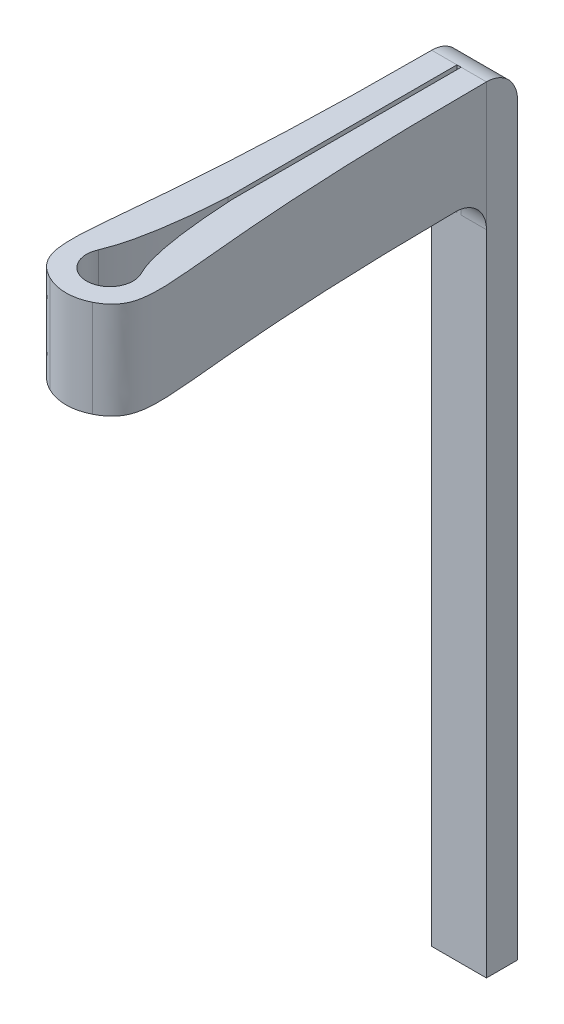
SolidWorks part; units mm, degrees
ref_plane "Front Plane" through (0, 0, 0) normal (0, 0, 1) x (1, 0, 0)
ref_plane "Top Plane" through (0, 0, 0) normal (0, 1, 0) x (1, 0, 0)
ref_plane "Right Plane" through (0, 0, 0) normal (1, 0, 0) x (0, 0, -1)
sketch "Sketch1" plane through (0, 0, 0) normal (0, 1, 0) x (1, 0, 0)
  line L0 (0, 0) -> (0, 6.2146) construction
  line L1 (-0.6908, 2.6065) -> (-0.2172, 3.7387) construction
  line L2 (-0.0683, 13.7149) -> (0.0683, 13.7149)
  line L3 (-0.0683, 13.7149) -> (-0.0683, 6.2146)
  line L5 (0.0683, 13.7149) -> (0.0683, 6.2146)
  line L6 (-0.2172, 3.7387) -> (-0.0683, 6.2146) construction
  line L9 (0.6908, 2.6065) -> (0.2181, 3.4821) construction
  line L10 (0.2181, 3.4821) -> (0.0683, 6.2146) construction
  line L11 (-0.8958, 13.7149) -> (-0.8958, 4.5422) construction
  line L12 (-0.8958, 4.5422) -> (-1.5887, 2.2193) construction
  line L20 (-1.5887, 2.2193) -> (-2.0882, 1.3377) construction
  line L21 (-2.0882, 1.3377) -> (0, 0.7662) construction
  line L22 (0.8958, 13.7149) -> (0.8958, 4.5422) construction
  line L23 (0.8958, 4.5422) -> (1.5887, 2.2193) construction
  line L25 (1.5887, 2.2193) -> (2.0882, 1.3377) construction
  line L26 (2.0882, 1.3377) -> (0, 0.7662) construction
  line L27 (-0.8958, 13.7149) -> (0, 13.7149)
  line L28 (0.8958, 13.7149) -> (0, 13.7149)
  arc A0 (-0.6908, 2.6065) -> (0.6908, 2.6065) centre (0, 2.2849) ccw
  spline S3 degree 2 poles (0.6908, 2.6065) (0.2181, 3.4821) (0.0683, 6.2146) knots 0 0 0 1 1 1
  spline S4 degree 2 poles (-0.6908, 2.6065) (-0.2172, 3.7387) (-0.0683, 6.2146) knots 0 0 0 1 1 1
  spline S5 degree 4 poles (-0.8958, 13.7149) (-0.8958, 4.5422) (-1.5887, 2.2193) (-2.0882, 1.3377) (0, 0.7662) knots 0 0 0 0 0 1 1 1 1 1
  spline S6 degree 4 poles (0.8958, 13.7149) (0.8958, 4.5422) (1.5887, 2.2193) (2.0882, 1.3377) (0, 0.7662) knots 0 0 0 0 0 1 1 1 1 1
  point P8 (-0.508, -2.5134)
  point P18 (0.508, -2.5134)
  point P21 (0, -2.54)
  dimension "D1" = 1.524
  dimension "D2" = 11.43
extrude "Boss-Extrude1" add sketch "Sketch1" along normal blind 1.5875 and the other way blind 1.5875 contours S6 L28 L5 S3 A0 S4 L3 L27 S5 region at (-0.2009, 0, -9.9647)
ref_axis "Axis1" through (0, 0, -2.032) along (0, 0, 1)
ref_plane "Plane1" through (0, 0, 2.54) normal (0, 0, 1) x (1, 0, 0)
ref_axis "Axis2" through (0, 1.7463, 2.54) along (0, -1, 0)
fillet "Fillet1" radius 1.524 1 edges at (0, 0, -0.7662)
ref_plane "Plane2" through (0, 0, -2.6065) normal (0, 0, -1) x (-1, 0, 0)
ref_plane "Plane3" through (0, 0, -3.1145) normal (0, 0, -1) x (-1, 0, 0)
sketch "Sketch2" plane through (0, 0, 0) normal (1, 0, 0) x (0, 0, -1)
  line L0 (13.7149, -1.5875) -> (13.7149, 1.5875) construction
  line L1 (13.7149, -1.5875) -> (13.7149, 1.5875)
  line L3 (13.7149, 1.5875) -> (14.7309, 1.5875)
  line L4 (13.7149, 1.5875) -> (13.7149, -23.8125)
  line L5 (13.7149, -23.8125) -> (14.7309, -23.8125)
  line L6 (14.7309, 1.5875) -> (14.7309, -23.8125)
  dimension "D1" = 1.016
  dimension "D2" = 25.4
extrude "Boss-Extrude2" add sketch "Sketch2" along normal up to vertex (0.8958 mm away) and the other way up to vertex (0.8958 mm away) contours L6 L3 L1 L4 L5 region at (0, -11.1125, -14.2229) up to point (0.8958, 1.5875, -13.7149) other way up to point (-0.8958, 1.5875, -13.7149)
fillet "Fillet2" radius 1.016 3 edges at (0, 1.5875, -14.7309)
ref_point "Point1"
